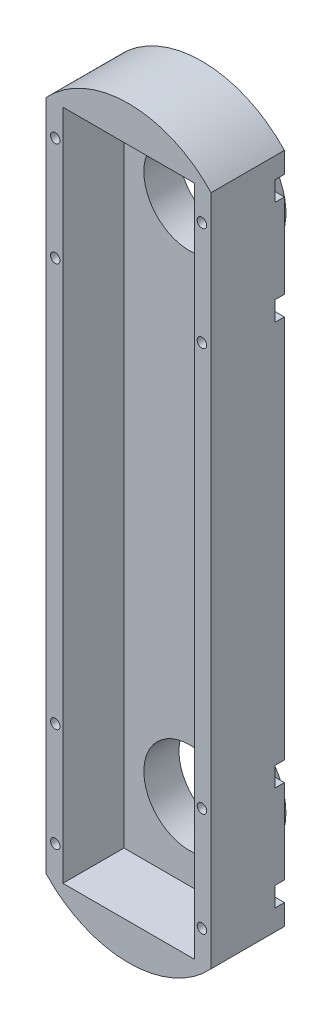
SolidWorks part; units mm, degrees
ref_plane "前视基准面" through (0, 0, 0) normal (0, 0, 1) x (1, 0, 0)
ref_plane "上视基准面" through (0, 0, 0) normal (0, 1, 0) x (1, 0, 0)
ref_plane "右视基准面" through (0, 0, 0) normal (1, 0, 0) x (0, 0, -1)
sketch "草图1" plane through (0, 0, 0) normal (0, 0, 1) x (1, 0, 0)
  line L1 (-27, 110) -> (27, 110)
  line L2 (-27, 110) -> (-27, -110)
  line L3 (-27, -110) -> (27, -110)
  line L4 (27, 110) -> (27, -110)
  line L5 (0, -110) -> (0, 110) construction
  line L6 (-27, 0) -> (27, 0) construction
  point P0 (0, 0)
  dimension "D1" = 220
  dimension "D2" = 54
extrude "凸台-拉伸1" add sketch "草图1" along normal blind 24
sketch "草图2" plane through (0, 0, 24) normal (0, 0, 1) x (1, 0, 0)
  line L0 (-27, 110) -> (-27, -110) construction
  line L1 (27, 110) -> (-27, 110) construction
  line L3 (-24, 100) -> (24, 100) construction
  line L5 (0, 0) -> (-70.719, 0) construction
  circle A0 centre (-24, 100) radius 1.55
  circle A1 centre (24, 100) radius 1.55
  circle A2 centre (24, 66) radius 1.55
  circle A3 centre (-24, 66) radius 1.55
  circle A4 centre (24, -100) radius 1.55
  circle A5 centre (24, -66) radius 1.55
  circle A6 centre (-24, -66) radius 1.55
  circle A7 centre (-24, -100) radius 1.55
  dimension "D1" = 3.1
  dimension "D6" = 48
  dimension "D2" = 3
  dimension "D3" = 10
  dimension "D7" = 34
  dimension "D4" = 2
  dimension "D5" = 2
extrude "切除-拉伸1" cut sketch "草图2" against normal through all
sketch "草图3" plane through (0, 0, 24) normal (0, 0, 1) x (1, 0, 0)
  line L0 (27, 110) -> (-27, 110) construction
  line L1 (-27, 110) -> (27, 110)
  line L2 (-27, -110) -> (27, -110) construction
  line L3 (-27, -110) -> (27, -110)
  arc A1 (-27, 110) -> (27, 110) centre (0, 84.9952) cw
  arc A2 (-27, -110) -> (27, -110) centre (0, -84.9952) ccw
  dimension "D1" = 36.8
extrude "凸台-拉伸2" add sketch "草图3" against normal up to surface (24 mm away) up to face at (22.45, -100, 0)
sketch "草图5" plane through (0, 0, 24) normal (0, 0, 1) x (1, 0, 0)
  line L0 (21.5, 110) -> (21.5, -110)
  line L2 (21.5, -110) -> (-21.5, -110)
  line L3 (-21.5, -110) -> (-21.5, 110)
  line L4 (0, 110) -> (0, -34.0506) construction
  line L5 (-21.5, 110) -> (21.5, 110)
  line L6 (0, 0) -> (-48.8779, 0) construction
  dimension "D1" = 220
  dimension "D2" = 43
extrude "切除-拉伸3" cut sketch "草图5" against normal blind 20 contours L4 L2 L0 | L4 L3 region at (0, 0, 24)
sketch "草图6" plane through (0, 0, 0) normal (0, 0, -1) x (-1, 0, 0)
  line L0 (-27, 69.2) -> (-24, 69.2)
  line L1 (-27, -110) -> (-27, 110) construction
  line L2 (-24, 62.8) -> (-27, 62.8)
  line L3 (-27, 69.2) -> (-27, 62.8)
  line L4 (-27, 103.2) -> (-27, 96.8)
  line L5 (-24, 96.8) -> (-27, 96.8)
  line L6 (-27, 103.2) -> (-24, 103.2)
  line L7 (-27, 69.2) -> (-27, 103.2) construction
  line L8 (0, 40.7864) -> (0, -44.4319) construction
  line L9 (27, 69.2) -> (24, 69.2)
  line L10 (24, 62.8) -> (27, 62.8)
  line L11 (27, 69.2) -> (27, 62.8)
  line L12 (27, 103.2) -> (24, 103.2)
  line L13 (24, 96.8) -> (27, 96.8)
  line L14 (27, 103.2) -> (27, 96.8)
  line L15 (0, 0) -> (-54.1071, 0) construction
  line L16 (27, -69.2) -> (27, -62.8)
  line L17 (24, -62.8) -> (27, -62.8)
  line L18 (27, -69.2) -> (24, -69.2)
  line L19 (27, -103.2) -> (27, -96.8)
  line L20 (24, -96.8) -> (27, -96.8)
  line L21 (27, -103.2) -> (24, -103.2)
  line L22 (-27, -103.2) -> (-24, -103.2)
  line L23 (-24, -96.8) -> (-27, -96.8)
  line L24 (-27, -103.2) -> (-27, -96.8)
  line L25 (-27, -69.2) -> (-24, -69.2)
  line L26 (-24, -62.8) -> (-27, -62.8)
  line L27 (-27, -69.2) -> (-27, -62.8)
  arc A0 (-24, 69.2) -> (-24, 62.8) centre (-24, 66) cw
  circle A1 centre (-24, 66) radius 1.55 construction
  arc A2 (-24, 103.2) -> (-24, 96.8) centre (-24, 100) cw
  arc A3 (24, 69.2) -> (24, 62.8) centre (24, 66) ccw
  arc A4 (24, 103.2) -> (24, 96.8) centre (24, 100) ccw
  arc A5 (24, -69.2) -> (24, -62.8) centre (24, -66) cw
  arc A6 (24, -103.2) -> (24, -96.8) centre (24, -100) cw
  arc A7 (-24, -103.2) -> (-24, -96.8) centre (-24, -100) ccw
  arc A8 (-24, -69.2) -> (-24, -62.8) centre (-24, -66) ccw
  dimension "D1" = 3.2
  dimension "D3" = 34
  dimension "D2" = 2
extrude "切除-拉伸4" cut sketch "草图6" against normal blind 3
sketch "草图7" plane through (0, 0, 0) normal (0, 0, -1) x (-1, 0, 0)
  line L0 (-27, 110) -> (27, 110) construction
  line L1 (0, 0) -> (0, 29.7821) construction
  line L2 (-27, 103.2) -> (-27, 110) construction
  line L3 (27, 110) -> (27, 103.2) construction
  line L4 (0, 0) -> (-81.8231, 0) construction
  circle A1 centre (0, 85) radius 15
  circle A2 centre (0, -85) radius 15
  point P0 (0, 0)
  dimension "D2" = 30
  dimension "D1" = 25
extrude "切除-拉伸5" cut sketch "草图7" against normal through all
fillet "圆角1" [suppressed] radius 5
sketch "草图11" plane through (0, 0, 0) normal (0, 0, -1) x (-1, 0, 0)
  line L0 (0, 0) -> (-101.3892, 0) construction
  circle A0 centre (0, 85) radius 20
  circle A1 centre (0, 85) radius 15
  circle A2 centre (0, -85) radius 15
  circle A3 centre (0, -85) radius 20
  dimension "D1" = 40
  dimension "D2" = 30
extrude "凸台-拉伸3" add sketch "草图11" along normal blind 7.5
sketch "草图12" plane through (0, 0, 0) normal (0, 0, -1) x (-1, 0, 0)
  line L0 (0, 0) -> (57.2331, 0) construction
  circle A0 centre (0, 85) radius 21
  circle A1 centre (0, 85) radius 20
  circle A2 centre (0, -85) radius 20
  circle A3 centre (0, -85) radius 21
  dimension "D1" = 42
  dimension "D2" = 40
extrude "凸台-拉伸4" add sketch "草图12" along normal blind 0.5
